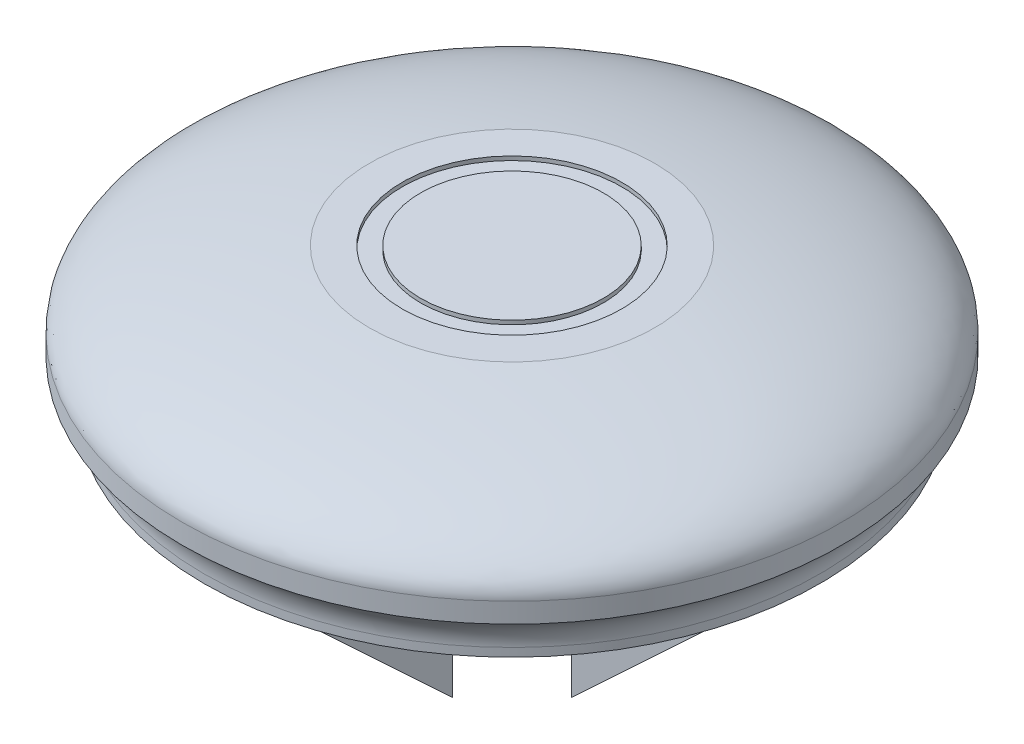
SolidWorks part; units mm, degrees
ref_plane "Front Plane" through (0, 0, 0) normal (0, 0, 1) x (1, 0, 0)
ref_plane "Top Plane" through (0, 0, 0) normal (0, 1, 0) x (1, 0, 0)
ref_plane "Right Plane" through (0, 0, 0) normal (1, 0, 0) x (0, 0, -1)
sketch "Sketch1" plane through (0, 0, 0) normal (0, 1, 0) x (1, 0, 0)
  line L0 (-59.9437, 50.8884) -> (-59.9437, 1.558)
  line L1 (-59.9437, 1.558) -> (-39.9437, 1.558)
  line L2 (-39.9437, 50.8884) -> (-39.9437, 1.558)
  line L3 (24.3866, -33.442) -> (-24.9437, -33.442)
  line L4 (24.3866, -13.442) -> (-24.9437, -13.442)
  line L5 (-24.9437, -13.442) -> (-24.9437, -33.442)
  line L6 (-59.9437, -97.7723) -> (-59.9437, -48.442)
  line L7 (-39.9437, -97.7723) -> (-39.9437, -48.442)
  line L8 (-39.9437, -48.442) -> (-59.9437, -48.442)
  line L9 (-124.2741, -13.442) -> (-74.9437, -13.442)
  line L10 (-124.2741, -33.442) -> (-74.9437, -33.442)
  line L11 (-74.9437, -33.442) -> (-74.9437, -13.442)
  arc A0 (-59.9437, 50.8884) -> (-124.2741, -13.442) centre (-49.9437, -23.442) ccw
  arc A1 (-124.2741, -33.442) -> (-59.9437, -97.7723) centre (-49.9437, -23.442) ccw
  arc A2 (-39.9437, -97.7723) -> (24.3866, -33.442) centre (-49.9437, -23.442) ccw
  arc A3 (24.3866, -13.442) -> (-39.9437, 50.8884) centre (-49.9437, -23.442) ccw
  circle A4 centre (-49.9437, -23.442) radius 82.8322
  point P1 (-49.9437, 1.558)
extrude "Boss-Extrude1" add sketch "Sketch1" along normal blind 5
ref_plane "Plane1" through (0, 0, 23.442) normal (0, 0, 1) x (1, 0, 0)
sketch "Sketch2" plane through (0, 0, 23.442) normal (0, 0, 1) x (1, 0, 0)
  line L0 (-49.9437, 5) -> (-49.9437, 25.9109)
  line L1 (32.8884, 5) -> (-132.7759, 5) construction
  line L2 (-49.9437, 5) -> (32.8884, 5)
  ellipse E0 centre (-49.9437, 5) end of major axis (32.8884, 5) minor radius 20.9109 (32.8884, 5) -> (-49.9437, 25.9109) ccw
revolve "Revolve1" add sketch "Sketch2" angle 360 about L0
sketch "Sketch3" plane through (0, 0, 23.442) normal (0, 0, 1) x (1, 0, 0)
  line L1 (-96.5274, 27.971) -> (-3.3601, 27.971)
  line L2 (-96.5274, 27.971) -> (-96.5274, 23.8509)
  line L3 (-96.5274, 23.8509) -> (-3.3601, 23.8509)
  line L4 (-3.3601, 27.971) -> (-3.3601, 23.8509)
  line L5 (-96.5274, 27.971) -> (-3.3601, 23.8509) construction
  line L6 (-96.5274, 23.8509) -> (-3.3601, 27.971) construction
  point P0 (-49.9437, 25.9109)
extrude "Cut-Extrude1" cut sketch "Sketch3" against normal mid plane 150
sketch "Sketch4" plane through (0, 23.8509, 0) normal (0, 1, 0) x (1, 0, 0)
  line L0 (-2.75, -23.442) -> (2.75, -23.442) construction
  circle A0 centre (-49.9437, -23.442) radius 22.9729
  circle A1 centre (-49.9437, -23.442) radius 27.5983
extrude "Cut-Extrude2" cut sketch "Sketch4" against normal blind 1
sketch "Sketch5" plane through (0, 0, 0) normal (0, -1, 0) x (1, 0, 0)
  line L0 (-59.9437, 97.7723) -> (-59.9437, 48.442)
  line L1 (-59.9437, 48.442) -> (-39.9437, 48.442)
  line L2 (-39.9437, 48.442) -> (-39.9437, 97.7723)
  line L3 (-24.9437, 33.442) -> (24.3866, 33.442)
  line L4 (24.3866, 13.442) -> (-24.9437, 13.442)
  line L5 (-24.9437, 13.442) -> (-24.9437, 33.442)
  line L6 (-74.9437, 33.442) -> (-74.9437, 13.442)
  line L7 (-74.9437, 13.442) -> (-124.2741, 13.442)
  line L8 (-74.9437, 33.442) -> (-124.2741, 33.442)
  line L9 (-59.9437, -1.558) -> (-39.9437, -1.558)
  line L10 (-39.9437, -1.558) -> (-39.9437, -50.8884)
  line L11 (-59.9437, -1.558) -> (-59.9437, -50.8884)
  arc A0 (-39.9437, -50.8884) -> (24.3866, 13.442) centre (-49.9437, 23.442) ccw
  arc A1 (-124.2741, 13.442) -> (-59.9437, -50.8884) centre (-49.9437, 23.442) ccw
  arc A2 (-59.9437, 97.7723) -> (-124.2741, 33.442) centre (-49.9437, 23.442) ccw
  arc A3 (24.3866, 33.442) -> (-39.9437, 97.7723) centre (-49.9437, 23.442) ccw
  circle A4 centre (-49.9437, 23.442) radius 77.4336
extrude "Boss-Extrude2" add sketch "Sketch5" along normal blind 11
fillet "Fillet1" radius 10 1 edges at (-49.9437, 0, 100.8756)
sketch "Sketch6" plane through (0, -11, 0) normal (0, -1, 0) x (1, 0, 0)
  line L1 (-24.9437, 33.442) -> (24.3866, 33.442)
  line L2 (-24.9437, 33.442) -> (-24.9437, 13.442)
  line L3 (-24.9437, 13.442) -> (24.3866, 13.442)
  line L4 (24.3866, 33.442) -> (24.3866, 13.442)
extrude "Boss-Extrude3" add sketch "Sketch6" along normal blind 46
sketch "Sketch7" plane through (0, 0, 33.442) normal (0, 0, 1) x (1, 0, 0)
  line L0 (24.3866, -11) -> (-24.9437, -57)
  line L1 (-24.9437, -57) -> (24.3866, -57)
  line L2 (24.3866, -57) -> (24.3866, -11)
extrude "Cut-Extrude3" cut sketch "Sketch7" against normal blind 46
pattern_circular "CirPattern1" count 4 over 360 about axis through (-49.9437, 5, 23.442) along (0, -1, 0) of "Boss-Extrude3", "Cut-Extrude3"
